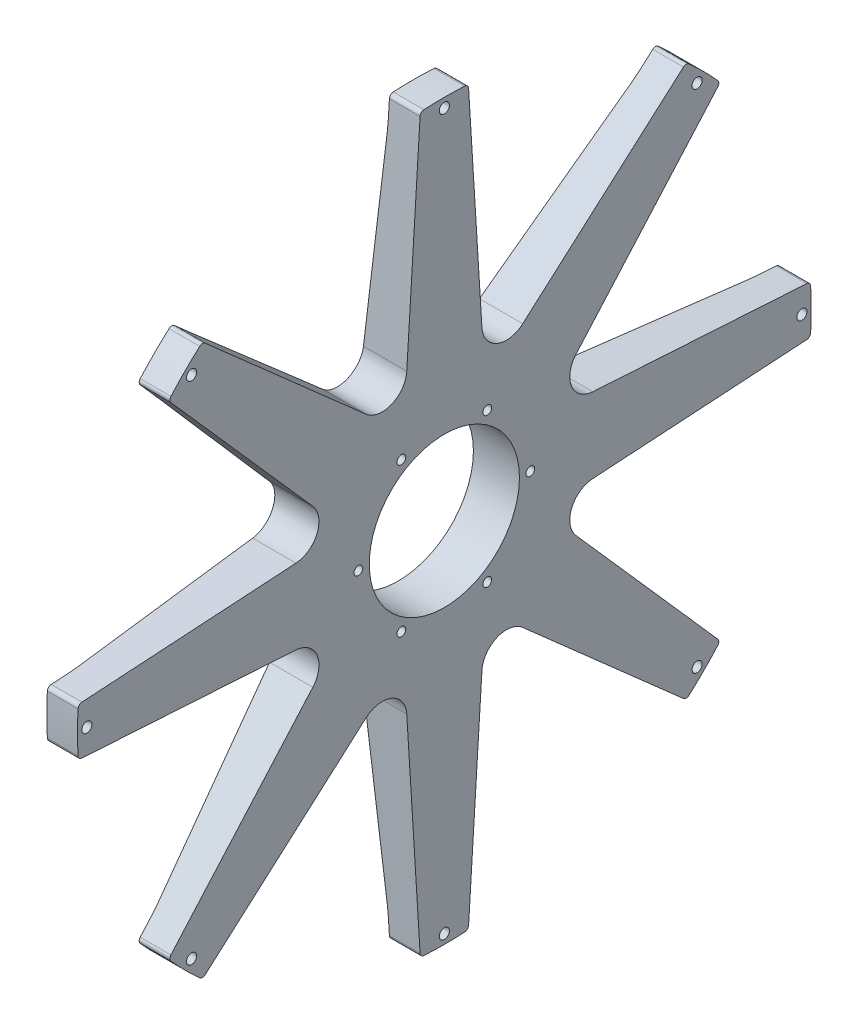
SolidWorks part; units mm, degrees
note: '?' marks a value the reader was unsure of. The reader was unsure of these and kept them because the rebuilt part matched: shared geometry of "Rim Base<4>".
material "6061-T6 (SS)"
ref_plane "Front Plane" through (0, 0, 0) normal (1, 0, 0) x (0, 1, 0)
ref_plane "Top Plane" through (0, 0, 0) normal (0, 0, 1) x (0, 1, 0)
ref_plane "Right Plane" through (0, 0, 0) normal (0, 1, 0) x (-1, 0, 0)
sketch "Rim Base" plane through (1321.9127, 0, 0) normal (-1, 0, 0) x (0, -1, 0)
  line L0 (-601.9127, 917.067) -> (-621.8122, 869.0252) construction
  line L1 (-601.9127, 742.367) -> (-601.9127, 737.792)
  line L2 (-601.9127, 737.792) -> (-601.9127, 737.592) construction
  line L3 (-601.9127, 917.067) -> (-582.0132, 869.0252) construction
  line L4 (-601.9127, 917.067) -> (-601.9127, 742.367)
  line L5 (-621.8122, 869.0252) -> (-606.8221, 747.1987)
  line L6 (-601.9127, 742.367) -> (-589.9127, 742.367) construction
  line L7 (-607.2191, 747.1498) -> (-606.8221, 747.1987) construction
  line L8 (-601.9127, 917.067) -> (-601.9127, 969.067)
  line L9 (-590.064, 739.9415) -> (-582.0132, 869.0252)
  line L10 (-582.0132, 869.0252) -> (-587.2177, 738.1946) construction
  circle A0 centre (-601.9127, 742.367) radius 2.4892
  circle A1 centre (-601.9127, 742.367) radius 2.4892 construction
  circle A2 centre (-601.9127, 742.367) radius 4.575
  arc A3 (-616.6077, 738.1946) -> (-587.2177, 738.1946) centre (-601.9127, 917.067) ccw construction
  arc A4 (-616.6077, 738.1946) -> (-587.2177, 738.1946) centre (-601.9127, 917.067) ccw construction
  circle A5 centre (-601.9127, 1091.767) radius 2.4892 construction
  circle A6 centre (-601.9127, 1091.767) radius 2.4892
  circle A7 centre (-601.9127, 917.067) radius 36.7
  circle A8 centre (-601.9127, 917.067) radius 36.5 construction
  circle A9 centre (-601.9127, 917.067) radius 36.5 construction
  circle A10 centre (-601.9127, 917.067) radius 36.5
  circle A11 centre (-601.9127, 917.067) radius 52
  arc A12 (-557.9844, 944.8934) -> (-599.7785, 969.0232) centre (-601.9127, 917.067) ccw construction
  arc A13 (-606.8221, 747.1987) -> (-606.4872, 742.3024) centre (-651.8191, 741.662) cw
  arc A14 (-590.064, 739.9415) -> (-591.9489, 738.0691) centre (-592.0601, 740.066) cw
  arc A15 (-601.9127, 737.792) -> (-591.9489, 738.0691) centre (-601.9127, 917.067) ccw
  circle A16 centre (-638.2858, 938.067) radius 2.1526 construction
  circle A17 centre (-638.2858, 896.067) radius 2.1527 construction
  circle A18 centre (-601.9127, 875.067) radius 2.1526 construction
  circle A19 centre (-565.5396, 896.067) radius 2.1526 construction
  circle A20 centre (-565.5396, 938.067) radius 2.1527 construction
  circle A21 centre (-601.9127, 959.067) radius 2.1526 construction
  circle A22 centre (-638.2858, 938.067) radius 2.1526
  circle A23 centre (-638.2858, 896.067) radius 2.1526
  circle A24 centre (-601.9127, 875.067) radius 2.1526
  circle A25 centre (-565.5396, 896.067) radius 2.1526
  circle A26 centre (-565.5396, 938.067) radius 2.1526
  circle A27 centre (-601.9127, 959.067) radius 2.1526
  dimension "D1" = 0
  dimension "D2" = 0.2
  dimension "D3" = 0.2
  dimension "D4" = 12
  dimension "D7" = 2
  dimension "D5" = 22.5
  dimension "D6" = 0.4
extrude "Boss-Extrude1" add sketch "Rim Base" along normal blind 22.5
ref_axis "Axis1" through (1299.4127, 601.9127, 917.067) along (1, 0, 0)
ref_axis "Axis2" through (1299.4127, 601.9127, 742.367) along (1, 0, 0)?
ref_plane "Plane1" through (0, 601.9127, 0) normal (0, 1, 0) x (1, 0, 0)
sketch "Sketch1" plane through (0, 601.9127, 0) normal (0, 1, 0) x (1, 0, 0)
  line L0 (1321.9127, -865.067) -> (1299.4127, -865.067)
  line L1 (1299.4127, -880.367) -> (1299.4127, -744.8562) construction
  line L2 (1299.4127, -880.367) -> (1299.4127, -744.8562)
  line L6 (1299.4127, -739.8778) -> (1299.4127, -744.8562) construction
  line L7 (1306.9127, -737.792) -> (1306.9127, -747.792)
  line L9 (1306.7337, -753.1409) -> (1299.5918, -859.718)
  line L12 (1299.4127, -739.8778) -> (1299.4127, -737.792) construction
  line L13 (1299.4127, -737.792) -> (1321.9127, -737.792) construction
  line L15 (1299.4127, -739.8778) -> (1299.4127, -744.8562)
  line L16 (1299.4127, -739.8778) -> (1299.4127, -737.792)
  line L17 (1299.4127, -737.792) -> (1321.9127, -737.792)
  line L18 (1321.9127, -739.8778) -> (1321.9127, -737.792) construction
  arc A0 (1306.9127, -747.792) -> (1306.7337, -753.1409) centre (1226.9127, -747.792) cw
  arc A1 (1299.5918, -859.718) -> (1299.4127, -865.067) centre (1379.4127, -865.067) ccw
  dimension "D3" = 80
  dimension "D1" = 15
  dimension "D2" = 10
revolve "Cut-Revolve1" cut sketch "Sketch1" angle 360 about axis through (1299.4127, 601.9127, 917.067) along (1, 0, 0)
mirror "Mirror1" about plane through (1299.4127, 601.9127, 0) normal (0, -1, 0) of bodies 104
pattern_circular "CirPattern1" count 8 every 45 about axis through (0, 601.9127, 917.067) along (1, 0, 0) of bodies 113 104
combine bodies "Combine1" bodies to combine 113 106 107 108 109 110 111 112
extrude "Cut-Extrude1" cut sketch "Rim Base<4>" along normal through all contours L8 A27 | L8 A27 | A26 | A25 | L4 A24 | L4 A24 | A23 | A22
sketch "Rim Base<4>" plane through (1321.9127, 0, 0) normal (-1, 0, 0) x (0, -1, 0) same geometry as "Rim Base"
fillet "Fillet2" radius 12 8 edges at (1310.6627, 582.0132, 965.1087) (1310.6627, 553.871, 936.9665) (1310.6627, 553.871, 897.1674) (1310.6627, 582.0132, 869.0252) (1310.6627, 621.8122, 869.0252) (1310.6627, 649.9544, 897.1674) (1310.6627, 649.9544, 936.9665) (1310.6627, 621.8122, 965.1087)
equation "\"tol\"= 0.2mm"
